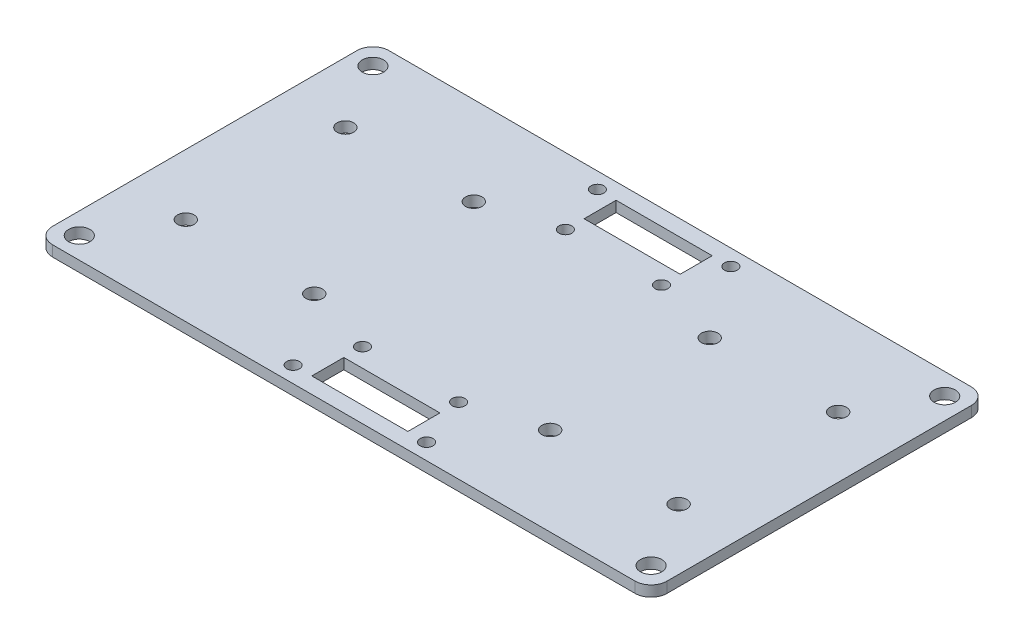
SolidWorks part; units mm, degrees
ref_plane "Plano frontal" through (0, 0, 0) normal (0, 0, 1) x (1, 0, 0)
ref_plane "Plano superior" through (0, 0, 0) normal (0, 1, 0) x (1, 0, 0)
ref_plane "Plano direito" through (0, 0, 0) normal (1, 0, 0) x (0, 0, -1)
sketch "Esboço1" plane through (0, 0, 0) normal (0, 1, 0) x (1, 0, 0)
  line L7 (-57.5484, 31.5) -> (57.5484, 31.5)
  line L8 (57.5484, 31.5) -> (57.5484, -31.5)
  line L9 (57.5484, -31.5) -> (-57.5484, -31.5)
  line L10 (-57.5484, -31.5) -> (-57.5484, 31.5)
  line L11 (0, 31.5) -> (0, -31.5) construction
  line L12 (-57.5484, 0) -> (57.5484, 0) construction
  dimension "D1" = 63
  dimension "D2" = 115.0968
extrude "Ressalto-extrusão1" add sketch "Esboço1" along normal blind 2
sketch "Esboço2" plane through (0, 2, 0) normal (0, 1, 0) x (1, 0, 0)
  line L0 (-57.5484, 0) -> (57.5484, 0) construction
  line L1 (-57.5484, 31.5) -> (-57.5484, -31.5) construction
  line L2 (-57.5484, -31.5) -> (57.5484, -31.5) construction
  line L5 (57.5484, -31.5) -> (57.5484, 31.5) construction
  line L6 (0, -31.5) -> (0, 31.5) construction
  line L7 (57.5484, 31.5) -> (-57.5484, 31.5) construction
  circle A8 centre (-46.1536, -14.945) radius 1.55
  circle A10 centre (-22.0936, -14.94) radius 1.55
  circle A11 centre (22.0936, -14.94) radius 1.55
  circle A12 centre (46.1536, -14.945) radius 1.55
  circle A13 centre (46.1536, 14.945) radius 1.55
  circle A14 centre (22.0936, 14.94) radius 1.55
  circle A15 centre (-22.0936, 14.94) radius 1.55
  circle A16 centre (-46.1536, 14.945) radius 1.55
  dimension "D1" = 16.555
  dimension "D3" = 3.1
  dimension "D4" = 16.56
  dimension "D2" = 24.06
  dimension "D5" = 11.3948
extrude "Corte-extrusão1" cut sketch "Esboço2" against normal through all
sketch "Esboço3" plane through (0, 0, 0) normal (0, -1, 0) x (1, 0, 0)
  line L0 (0, 31.5) -> (0, 28.5) construction
  line L1 (-57.5484, 31.5) -> (57.5484, 31.5) construction
  line L2 (-9, 28.5) -> (9, 28.5)
  line L3 (9, 28.5) -> (9, 22.5)
  line L4 (-9, 28.5) -> (-9, 22.5)
  line L5 (-9, 22.5) -> (9, 22.5)
  line L6 (-57.5484, 0) -> (57.5484, 0) construction
  line L7 (-57.5484, -31.5) -> (-57.5484, 31.5) construction
  line L8 (57.5484, 31.5) -> (57.5484, -31.5) construction
  line L9 (9, 28.5) -> (9, 22.5)
  line L10 (-9, 28.5) -> (-9, 22.5)
  line L11 (9, 28.5) -> (9, 22.5)
  line L12 (-9, 28.5) -> (-9, 22.5)
  line L13 (9, 28.5) -> (9, 22.5)
  line L14 (-9, 28.5) -> (-9, 22.5)
  line L15 (0, -31.5) -> (0, -28.5) construction
  line L16 (-9, -28.5) -> (-9, -22.5)
  line L17 (9, -28.5) -> (9, -22.5)
  line L18 (-9, -28.5) -> (-9, -22.5)
  line L19 (9, -28.5) -> (9, -22.5)
  line L20 (-9, -28.5) -> (-9, -22.5)
  line L21 (9, -28.5) -> (9, -22.5)
  line L22 (-9, -22.5) -> (9, -22.5)
  line L23 (-9, -28.5) -> (-9, -22.5)
  line L24 (9, -28.5) -> (9, -22.5)
  line L25 (-9, -28.5) -> (9, -28.5)
  point P8 (0, 28.5)
  point P22 (0, -28.5)
  dimension "D1" = 3
  dimension "D2" = 18
  dimension "D3" = 6
extrude "Corte-extrusão2" cut sketch "Esboço3" against normal through all contours L4 L5 L3 L2 | L16 L25 L17 L22 region at (0, 0, 25.5) region at (0, 0, -25.5)
sketch "Esboço5" plane through (0, 2, 0) normal (0, 1, 0) x (1, 0, 0)
  line L2 (57.5484, 31.5) -> (-57.5484, 31.5) construction
  line L3 (57.5484, -31.5) -> (57.5484, 31.5) construction
  line L4 (57.5484, 0) -> (-57.5484, 0) construction
  line L5 (-57.5484, 31.5) -> (-57.5484, -31.5) construction
  line L6 (0, 31.5) -> (0, -31.5) construction
  line L7 (-57.5484, -31.5) -> (57.5484, -31.5) construction
  line L8 (53.5484, -13.175) -> (53.5484, -27.5) construction
  line L9 (-53.5484, -13.175) -> (-53.5484, -27.5) construction
  line L10 (-53.5484, 21.175) -> (-53.5484, 35.5) construction
  circle A0 centre (53.5484, 27.5) radius 2
  circle A1 centre (53.5484, -27.5) radius 2
  circle A2 centre (-53.5484, -27.5) radius 2
  circle A3 centre (-53.5484, 27.5) radius 2
  dimension "D2" = 4
  dimension "D1" = 4
  dimension "D3" = 4
extrude "Corte-extrusão3" cut sketch "Esboço5" against normal through all
fillet "Filete1" radius 3 4 edges at (57.5484, 1, -31.5) (57.5484, 1, 31.5) (-57.5484, 1, 31.5) (-57.5484, 1, -31.5)
sketch "Esboço8" plane through (0, 2, 0) normal (0, 1, 0) x (1, 0, 0)
  line L0 (-57.5484, 28.5) -> (-57.5484, -28.5) construction
  line L1 (54.5484, 31.5) -> (-54.5484, 31.5) construction
  line L2 (0, 0) -> (0, 31.5) construction
  line L3 (57.5484, 0) -> (-57.5484, 0) construction
  line L4 (-54.5484, -31.5) -> (54.5484, -31.5) construction
  line L5 (57.5484, -28.5) -> (57.5484, 28.5) construction
  circle A0 centre (-12.4984, 28.5) radius 1.2
  circle A1 centre (12.4984, 28.5) radius 1.2
  circle A2 centre (12.4984, -28.5) radius 1.2
  circle A3 centre (-12.4984, -28.5) radius 1.2
  circle A8 centre (-8.9984, -19) radius 1.2
  circle A12 centre (8.9984, -19) radius 1.2
  circle A13 centre (8.9984, 19) radius 1.2
  circle A14 centre (-8.9984, 19) radius 1.2
  dimension "D1" = 2.4
  dimension "D4" = 2.4
  dimension "D5" = 12.5
  dimension "D6" = 48.55
  dimension "D2" = 45.05
  dimension "D3" = 3
extrude "Corte-extrusão4" cut sketch "Esboço8" against normal through all
